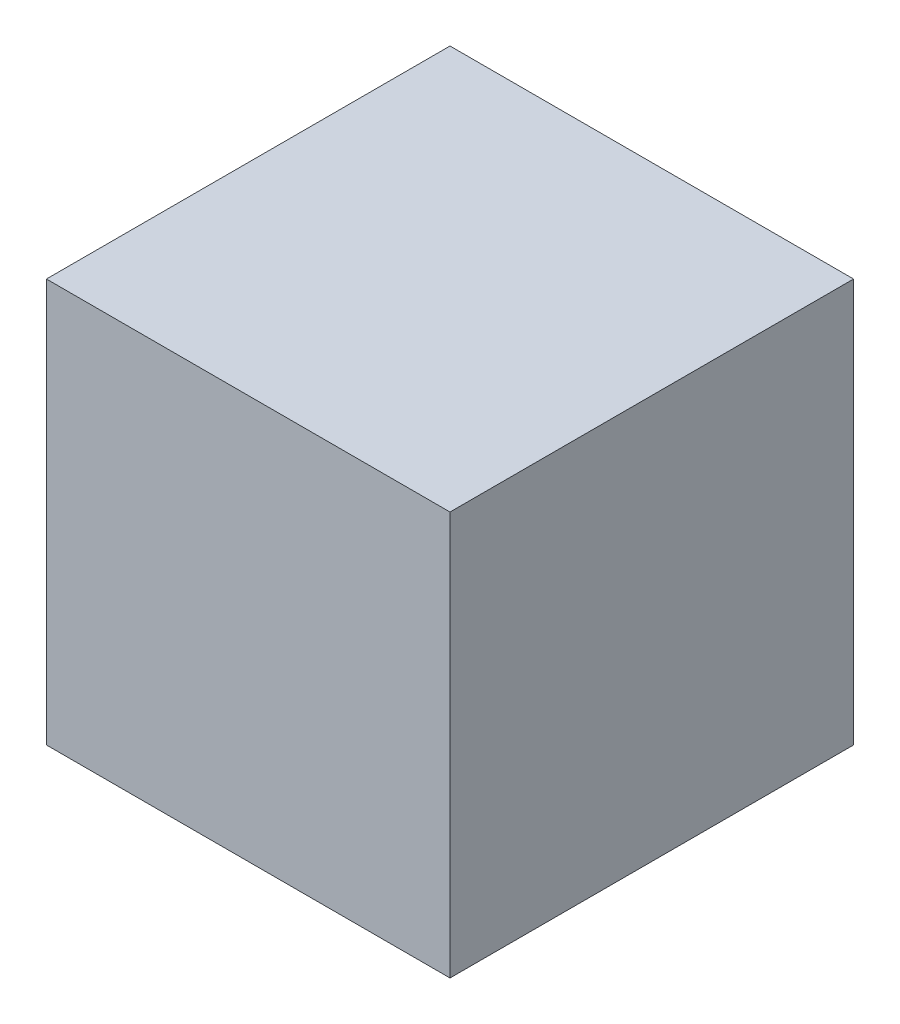
SolidWorks part; units mm, degrees
ref_plane "Front Plane" through (0, 0, 0) normal (0, 0, 1) x (1, 0, 0)
ref_plane "Top Plane" through (0, 0, 0) normal (0, 1, 0) x (1, 0, 0)
ref_plane "Right Plane" through (0, 0, 0) normal (1, 0, 0) x (0, 0, -1)
sketch "Sketch1" plane through (0, 0, 0) normal (0, 1, 0) x (1, 0, 0)
  line L1 (-500, -500) -> (500, -500)
  line L2 (-500, -500) -> (-500, 500)
  line L3 (-500, 500) -> (500, 500)
  line L4 (500, -500) -> (500, 500)
  line L5 (-500, -500) -> (500, 500) construction
  line L6 (-500, 500) -> (500, -500) construction
  point P0 (0, 0)
  dimension "D1" = 1000
  dimension "D2" = 1000
extrude "Boss-Extrude1" add sketch "Sketch1" along normal blind 500 and the other way blind 500
